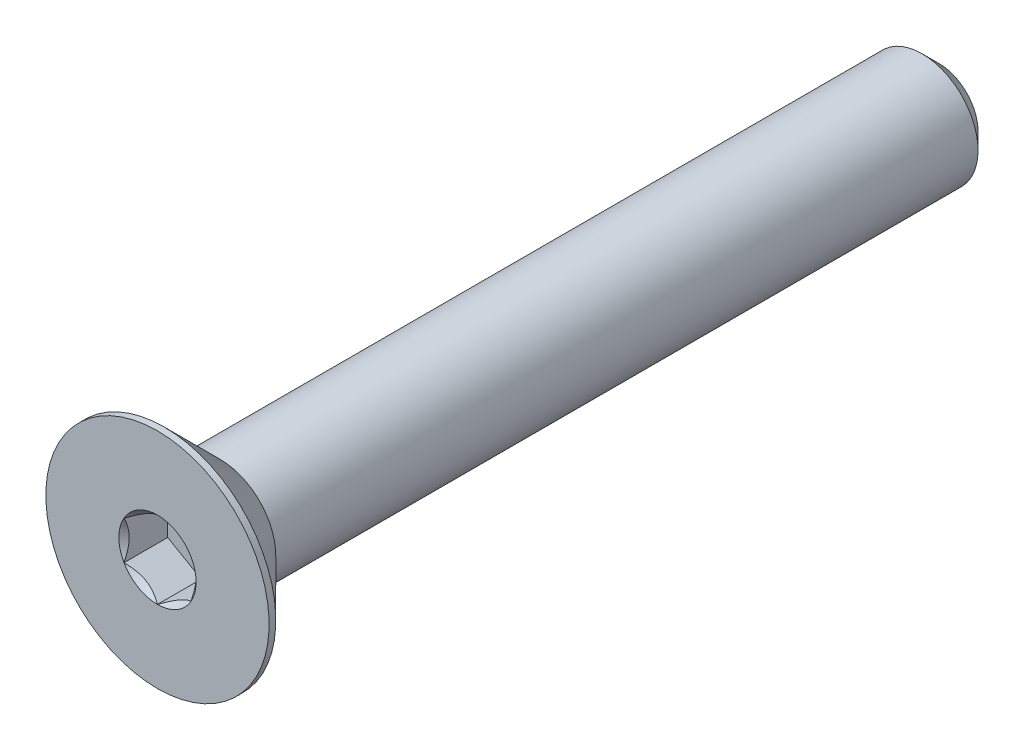
SolidWorks part; units mm, degrees
ref_plane "Front" through (0, 0, 0) normal (0, 0, 1) x (1, 0, 0)
ref_plane "Top" through (0, 0, 0) normal (0, 1, 0) x (1, 0, 0)
ref_plane "Right" through (0, 0, 0) normal (1, 0, 0) x (0, 0, -1)
sketch "Sketch1" plane through (0, 0, 0) normal (1, 0, 0) x (0, 0, -1)
  line L0 (-17.5, 5) -> (-17.2, 5) construction
  line L1 (-17.2, 5) -> (-14.7, 2.5) construction
  line L2 (-17.5, 2.5) -> (17.5, 2.5) construction
  line L3 (17.5, 2.5) -> (17.5, 0) construction
  line L4 (17.5, 0) -> (-17.5, 0) construction
  line L5 (-17.5, 0) -> (-17.5, 5) construction
  line L6 (-17.5, 5) -> (-17.5, -5) construction
  line L7 (17.5, 2.5) -> (17.5, -2.5) construction
  line L8 (-17.5, -5) -> (-17.2, -5) construction
  line L9 (-17.2, -5) -> (-14.7, -2.5) construction
  line L11 (-17.5, 2.5) -> (-17.5, 0) construction
  line L12 (-14.7, 2.5) -> (-14.7, 0) construction
  line L13 (17.45, 2.5866) -> (17.85, 1.8938) construction
  line L14 (17.85, 1.8938) -> (18.25, 2.5866) construction
  line L15 (18.25, 2.5866) -> (17.45, 2.5866) construction
  line L16 (17.85, 2.5866) -> (17.85, 2.5) construction
  line L17 (17.85, 2.5) -> (17.85, 1.9804) construction
  line L18 (17.85, 1.9804) -> (17.85, 1.8938) construction
  line L19 (17.85, 2.5433) -> (18.225, 2.5433) construction
  line L20 (17.85, 2.5433) -> (17.475, 2.5433) construction
  line L21 (17.5, 2.5) -> (18.2, 2.5) construction
  line L22 (17.8, 1.9804) -> (17.9, 1.9804) construction
  line L23 (17.5, -2.5) -> (-14.7, -2.5) construction
  point P10 (15.5, -2.5)
  point P24 (-9.7, 2.5)
  point P30 (0, 0)
  dimension "Head Diameter" = 10
  dimension "Head Height" = 2.8
  dimension "Length" = 35
  dimension "Countersink Angle" = 90
  dimension "Thread Pitch" = 0.8
  dimension "D2" = 0.1
  dimension "Minimum Thread Length" = 27.2
  dimension "Thread Size" = 5
  dimension "D1" = 2
sketch "Sketch2" plane through (0, 0, 0) normal (0, 0, 1) x (1, 0, 0)
  line L1 (0, 1.7321) -> (-1.5, 0.866) construction
  line L2 (-1.5, 0.866) -> (-1.5, -0.866) construction
  line L3 (-1.5, -0.866) -> (0, -1.7321) construction
  line L4 (0, -1.7321) -> (1.5, -0.866) construction
  line L5 (1.5, -0.866) -> (1.5, 0.866) construction
  line L6 (1.5, 0.866) -> (0, 1.7321) construction
  circle A0 centre (0, 0) radius 1.5 construction
  dimension "Drive Size" = 3
sketch "Sketch3" plane through (0, 0, 0) normal (1, 0, 0) x (0, 0, -1)
  line L0 (-17.5, 2.5) -> (17.5, 2.5)
  line L1 (17.5, 2.5) -> (17.5, 0)
  line L2 (17.5, 0) -> (-17.5, 0)
  line L3 (-17.5, 0) -> (-17.5, 2.5)
revolve "Revolve1" add sketch "Sketch3" angle 360 about L4
chamfer "Chamfer1" distance 0.75 angle 45 1 edges at (0, 2.5, -17.5)
sketch "Sketch6" plane through (0, 0, 0) normal (1, 0, 0) x (0, 0, -1)
  line L0 (-17.5, 5) -> (-17.2, 5)
  line L1 (-17.2, 5) -> (-14.7, 2.5)
  line L2 (-14.7, 2.5) -> (-14.7, 0)
  line L3 (-14.7, 0) -> (-17.5, 0)
  line L4 (-17.5, 0) -> (-17.5, 5)
revolve "Revolve2" add sketch "Sketch6" angle 360 about L4
sketch "Sketch8" plane through (0, 0, 17.5) normal (0, 0, 1) x (1, 0, 0)
  line L0 (0, 1.7321) -> (-1.5, 0.866) construction
  line L1 (1.5, 0.866) -> (0, 1.7321) construction
  line L2 (1.5, -0.866) -> (1.5, 0.866) construction
  line L3 (0, -1.7321) -> (1.5, -0.866) construction
  line L4 (-1.5, 0.866) -> (-1.5, -0.866) construction
  line L5 (-1.5, -0.866) -> (0, -1.7321) construction
  line L6 (0, 1.7321) -> (-1.5, 0.866)
  line L7 (1.5, 0.866) -> (0, 1.7321)
  line L8 (1.5, -0.866) -> (1.5, 0.866)
  line L9 (0, -1.7321) -> (1.5, -0.866)
  line L10 (-1.5, 0.866) -> (-1.5, -0.866)
  line L11 (-1.5, -0.866) -> (0, -1.7321)
extrude "Cut-Extrude1" cut sketch "Sketch8" against normal blind 1.96
sketch "Sketch9" plane through (0, 0, 17.5) normal (0, 0, 1) x (1, 0, 0)
  circle A0 centre (0, 0) radius 1.7321
extrude "Cut-Extrude2" cut sketch "Sketch9" against normal up to next (1.96 mm away) draft 45
ref_plane "Plane1" [suppressed] through (0, 0, 12.2) normal (0, 0, 1) x (1, 0, 0)
split "Split1" [suppressed] bodies to split 124
sketch "Sketch4" [suppressed] plane through (0, 0, -15) normal (0, 0, -1) x (-1, 0, 0)
  circle A0 centre (0, 0) radius 2.5 construction
  circle A1 centre (0, 0) radius 2.5
curve "Helix/Spiral1" [suppressed] pitch 0.8 height 28 turns 35
sketch "Sketch10" [suppressed] plane through (0, 0, 0) normal (1, 0, 0) x (0, 0, -1)
  line L0 (14.975, 2.5433) -> (15.725, 2.5433)
  line L1 (15.725, 2.5433) -> (15.4, 1.9804)
  line L2 (15.4, 1.9804) -> (15.3, 1.9804)
  line L3 (15.3, 1.9804) -> (14.975, 2.5433)
sweep "Cut-Sweep1" [suppressed] cut profiles "Sketch10" path "Helix/Spiral1"
equation "\"D2@Sketch1\" = \"Thread Pitch@Sketch1\" / 8"
equation "\"D4@Helix/Spiral1\"=\"Thread Pitch@Sketch1\""
equation "\"D3@Helix/Spiral1\"=\"Minimum Thread Length@Sketch1\"+\"Thread Pitch@Sketch1\""
equation "\"D1@Chamfer1\"=\"Thread Size@Sketch1\"*.15"
equation "\"D1@Cut-Extrude1\"=\"Head Height@Sketch1\"*.7"
equation "\"D1@Sketch1\"=\"Thread Pitch@Sketch1\"*2.5"
